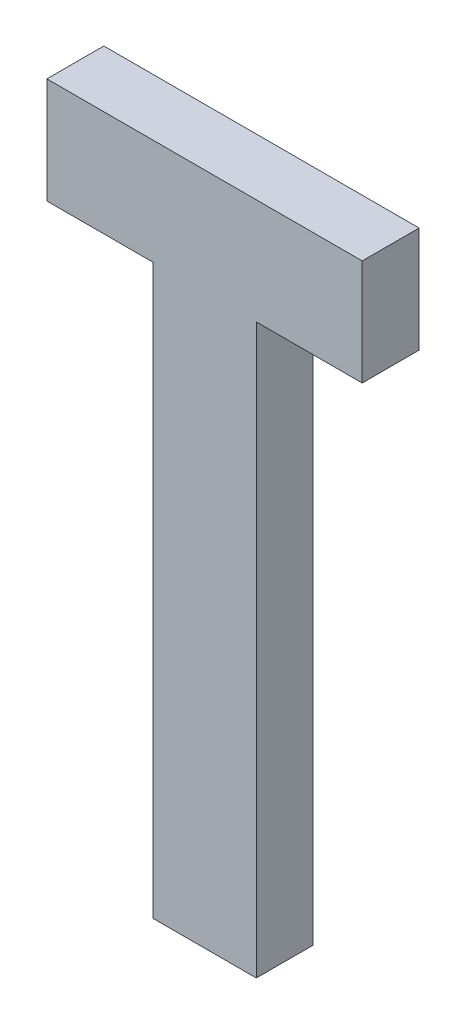
SolidWorks part; units mm, degrees
ref_plane "Front Plane" through (0, 0, 0) normal (0, 0, 1) x (1, 0, 0)
ref_plane "Top Plane" through (0, 0, 0) normal (0, 1, 0) x (1, 0, 0)
ref_plane "Right Plane" through (0, 0, 0) normal (1, 0, 0) x (0, 0, -1)
sketch "Sketch2" plane through (0, 0, 0) normal (0, 0, 1) x (1, 0, 0)
  line L0 (5, 24.8914) -> (15.2295, 24.8914)
  line L1 (-5, -30) -> (5, -30)
  line L2 (-5, -30) -> (-5, 24.8914)
  line L4 (5, -30) -> (5, 24.8914)
  line L5 (-5, -30) -> (0, 0) construction
  line L6 (0, 0) -> (5, -30) construction
  line L7 (-15.2295, 24.8914) -> (-5, 24.8914)
  line L8 (-15.2295, 24.8914) -> (-15.2295, 35.1086)
  line L9 (-15.2295, 35.1086) -> (15.2295, 35.1086)
  line L10 (15.2295, 24.8914) -> (15.2295, 35.1086)
  point P0 (0, 0)
  point P6 (0, 30)
  dimension "D1" = 10
extrude "Boss-Extrude2" add sketch "Sketch2" along normal blind 5.5
equation "\"D1@Boss-Extrude2\" = \"mat@V1.assembly\""
